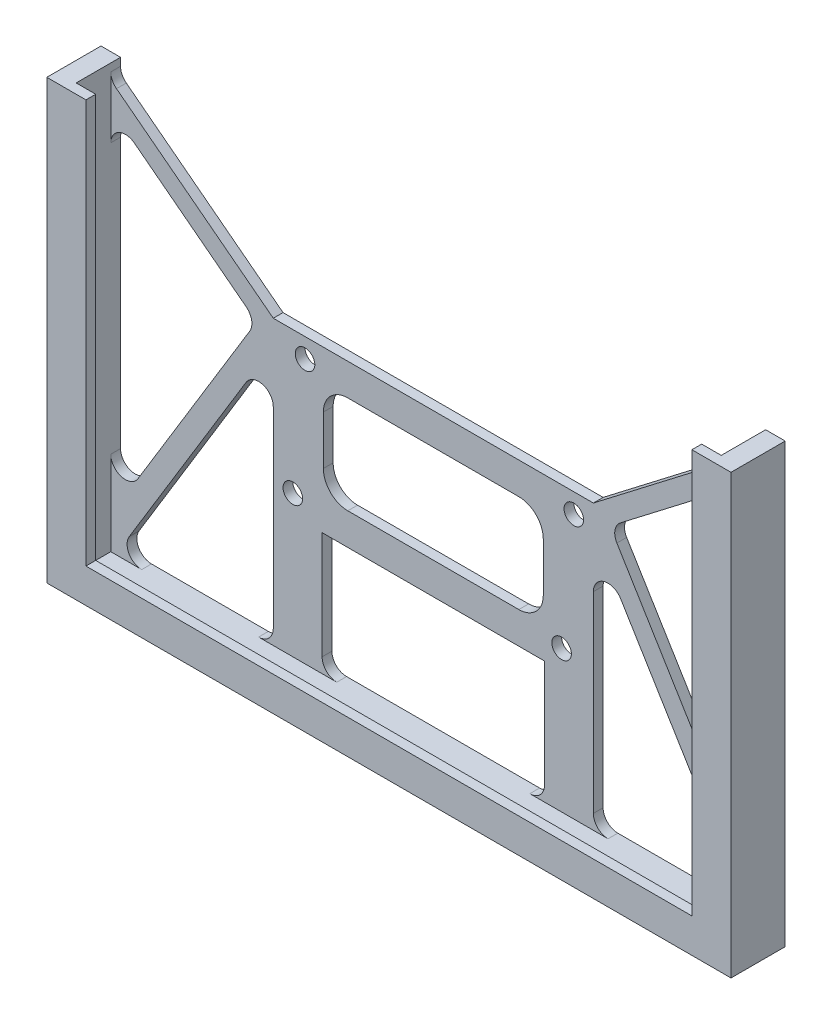
SolidWorks part; units mm, degrees
ref_plane "Front Plane" through (0, 0, 0) normal (0, 0, 1) x (1, 0, 0)
ref_plane "Top Plane" through (0, 0, 0) normal (0, 1, 0) x (1, 0, 0)
ref_plane "Right Plane" through (0, 0, 0) normal (1, 0, 0) x (0, 0, -1)
sketch "Sketch1" plane through (0, 0, 0) normal (0, 0, 1) x (1, 0, 0)
  line L1 (-8.255, 5.08) -> (74.93, 5.08)
  line L2 (-8.255, 5.08) -> (-8.255, -36.83)
  line L3 (-8.255, -36.83) -> (74.93, -36.83)
  line L4 (74.93, 5.08) -> (74.93, -36.83)
  line L5 (4.7625, -3.175) -> (61.9125, -3.175)
  line L6 (4.7625, -3.175) -> (4.7625, -28.575)
  line L7 (4.7625, -28.575) -> (61.9125, -28.575)
  line L8 (61.9125, -3.175) -> (61.9125, -28.575)
  circle A0 centre (0, 0) radius 2.54
  circle A1 centre (-3.175, -31.75) radius 2.54
  circle A2 centre (69.85, 0) radius 2.54
  circle A3 centre (66.675, -31.75) radius 2.54
  point P17 (33.3375, -3.175)
  point P18 (33.3375, 5.08)
  point P19 (4.7625, -15.875)
  point P20 (-8.255, -15.875)
  dimension "D1" = 5.08
  dimension "D2" = 3.175
  dimension "D3" = 3.175
  dimension "D4" = 69.85
  dimension "D5" = 31.75
  dimension "D6" = 5.08
  dimension "D7" = 5.08
  dimension "D8" = 5.08
  dimension "D9" = 5.08
  dimension "D10" = 57.15
  dimension "D11" = 25.4
extrude "Rover mount" add sketch "Sketch1" along normal blind 2.54 contours L4 L1 L2 L3 A3 A2 A1 A0 L5 L8 L7 L6 region at (33.3375, 4.1485, 0)
sketch "Sketch2" plane through (0, 0, 2.54) normal (0, 0, 1) x (1, 0, 0)
  line L1 (-50.4825, -68.58) -> (-8.255, -68.58)
  line L3 (-55.5625, -72.39) -> (122.2375, -72.39)
  line L5 (-8.255, 5.08) -> (74.93, 5.08) construction
  line L6 (-50.4825, -68.58) -> (-50.4825, 41.42)
  line L7 (-50.4825, 41.42) -> (-55.5625, 41.42)
  line L8 (-55.5625, 41.42) -> (-55.5625, -72.39)
  line L11 (122.2375, -72.39) -> (122.2375, 41.42)
  line L12 (122.2375, 41.42) -> (117.1575, 41.42)
  line L13 (117.1575, 41.42) -> (117.1575, -68.58)
  line L14 (-8.255, -36.83) -> (-8.255, -68.58)
  line L15 (-8.255, -36.83) -> (4.445, -36.83)
  line L16 (-8.255, -36.83) -> (74.93, -36.83) construction
  line L17 (4.445, -36.83) -> (4.445, -68.58)
  line L18 (74.93, -36.83) -> (62.23, -36.83)
  line L19 (62.23, -36.83) -> (62.23, -68.58)
  line L20 (74.93, -36.83) -> (74.93, -68.58)
  line L21 (4.445, -68.58) -> (62.23, -68.58)
  line L22 (74.93, -68.58) -> (117.1575, -68.58)
  point P5 (33.3375, -54.7817)
  point P6 (33.3375, 5.08)
  dimension "D1" = 110
  dimension "D2" = 177.8
  dimension "D3" = 5.08
  dimension "D4" = 3.81
  dimension "D5" = 12.7
  dimension "D6" = 31.75
extrude "Boss-Extrude2" add sketch "Sketch2" against normal up to surface (2.54 mm away) and the other way blind 9 up to face at (69.215, -31.75, 0)
sketch "Sketch3" plane through (0, 0, 2.54) normal (0, 0, 1) x (1, 0, 0)
  line L0 (-12.5823, 2.0541) -> (-55.5625, -68.58)
  line L1 (-55.5625, -68.58) -> (-49.2125, -68.58)
  line L2 (-8.255, -68.58) -> (-50.4825, -68.58) construction
  line L3 (-49.2125, -68.58) -> (-8.255, -1.27)
  line L4 (-8.255, 5.08) -> (-8.255, -36.83) construction
  line L5 (-8.255, -1.27) -> (-8.255, 5.08)
  line L6 (79.2573, 2.0541) -> (122.2375, -68.58)
  line L7 (122.2375, -68.58) -> (115.8875, -68.58)
  line L8 (115.8875, -68.58) -> (74.93, -1.27)
  line L9 (74.93, 5.08) -> (74.93, -36.83) construction
  line L10 (74.93, -1.27) -> (74.93, 5.08)
  line L11 (-55.5625, 41.42) -> (-55.5625, -72.39) construction
  line L12 (122.2375, -72.39) -> (122.2375, 41.42) construction
  line L13 (-55.5625, 41.42) -> (-8.255, 5.08)
  line L14 (-12.5823, 2.0541) -> (-55.5625, 35.07)
  line L15 (-55.5625, 35.07) -> (-55.5625, 41.42)
  line L16 (74.93, 5.08) -> (122.2375, 41.42)
  line L17 (122.2375, 41.42) -> (122.2375, 35.07)
  line L18 (122.2375, 35.07) -> (79.2573, 2.0541)
  point P25 (-14.7747, 3.7382)
  dimension "D1" = 6.35
extrude "Boss-Extrude3" add sketch "Sketch3" against normal blind 2.54
sketch "Sketch4" plane through (0, 0, 11.54) normal (0, 0, 1) x (1, 0, 0)
  line L0 (-55.5625, 41.42) -> (-45.4025, 41.42)
  line L1 (-45.4025, 41.42) -> (-45.4025, -63.5)
  line L2 (-45.4025, -63.5) -> (112.0775, -63.5)
  line L3 (112.0775, -63.5) -> (112.0775, 41.42)
  line L4 (112.0775, 41.42) -> (122.2375, 41.42)
  line L5 (122.2375, 41.42) -> (122.2375, -72.39)
  line L6 (122.2375, -72.39) -> (-55.5625, -72.39)
  line L7 (-55.5625, -72.39) -> (-55.5625, 41.42)
  line L8 (-50.4825, -68.58) -> (-50.4825, 41.42) construction
  line L9 (-8.255, -68.58) -> (-50.4825, -68.58) construction
  dimension "D1" = 5.08
  dimension "D2" = 5.08
extrude "Boss-Extrude4" add sketch "Sketch4" along normal blind 2.54
sketch "Sketch5" plane through (0, -36.83, 0) normal (0, 1, 0) x (1, 0, 0)
  line L0 (74.93, -2.54) -> (74.93, 0) construction
  line L1 (-8.255, -11.54) -> (74.93, -11.54)
  line L2 (-8.255, -11.54) -> (-8.255, -2.54)
  line L3 (-8.255, -2.54) -> (74.93, -2.54)
  line L4 (74.93, -11.54) -> (74.93, -2.54)
  line L5 (117.1575, -2.54) -> (74.93, -2.54) construction
  point P6 (0, 0)
extrude "Cut-Extrude1" cut sketch "Sketch5" against normal up to surface (31.75 mm away) up to face at (-35.9833, -68.58, 4.6933)
fillet "Fillet1" radius 3.81 16 edges at (62.23, -68.58, 1.27) (4.445, -68.58, 1.27) (117.1575, -60.2315, 1.27) (115.8875, -68.58, 1.27) (74.93, -68.58, 1.27) (74.93, -1.27, 1.27) (-8.255, -1.27, 1.27) (-8.255, -68.58, 1.27) (-49.2125, -68.58, 1.27) (-50.4825, -60.2315, 1.27) (117.1575, 31.1677, 1.27) (117.1575, 37.5177, 1.27) (79.2573, 2.0541, 1.27) (-12.5823, 2.0541, 1.27) (-50.4825, 31.1677, 1.27) (-50.4825, 37.5177, 1.27)
fillet "Fillet2" radius 6.35 4 edges at (4.7625, -3.175, 1.27) (4.7625, -28.575, 1.27) (61.9125, -3.175, 1.27) (61.9125, -28.575, 1.27)
